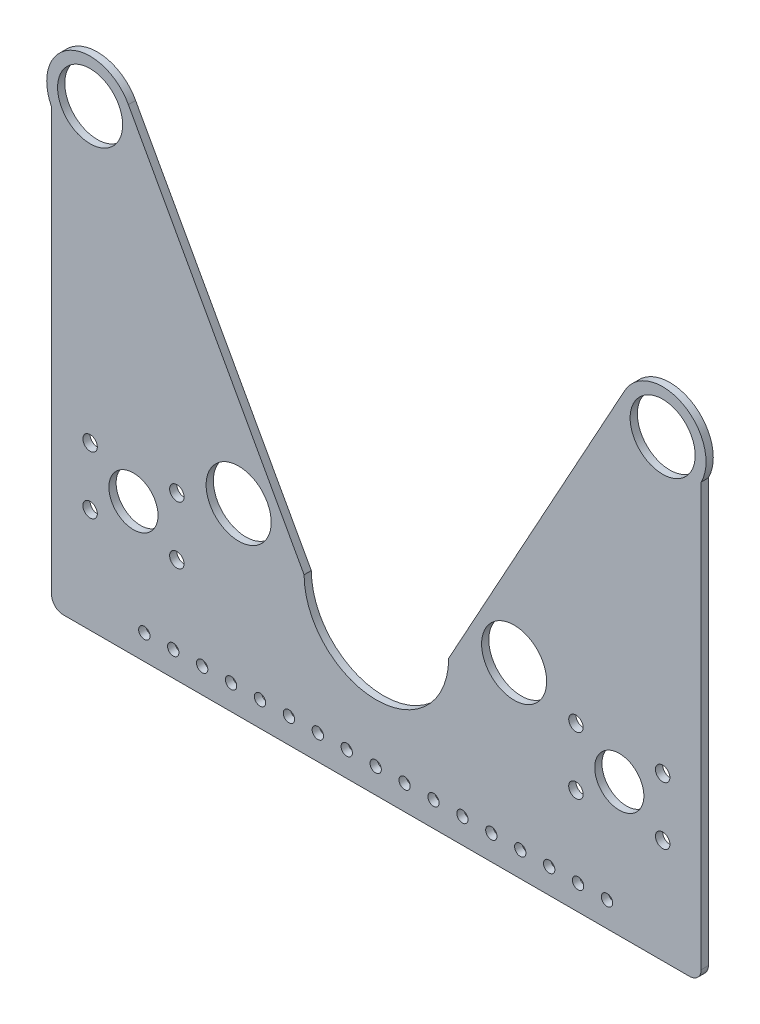
SolidWorks part; units mm, degrees
ref_plane "Front Plane" through (0, 0, 0) normal (0, 0, 1) x (1, 0, 0)
ref_plane "Top Plane" through (0, 0, 0) normal (0, 1, 0) x (1, 0, 0)
ref_plane "Right Plane" through (0, 0, 0) normal (1, 0, 0) x (0, 0, -1)
sketch "Sketch2" plane through (0, 0, 0) normal (0, 0, 1) x (1, 0, 0)
  line L0 (-106.68, -1085.9159) -> (-106.68, 48914.0841) construction
  line L1 (142.6324, 122.4629) -> (142.6324, -29.9371)
  line L2 (106.68, -1098.4025) -> (106.68, 48901.5975) construction
  line L3 (31.75, 0) -> (108.9183, 140.209)
  line L4 (0, -1082.0685) -> (0, 48917.9315) construction
  line L5 (-106.68, -44.45) -> (106.68, -44.45) construction
  line L6 (-106.68, -59.1767) -> (-106.68, -31.75)
  line L7 (0, -31.75) -> (106.68, -31.75) construction
  line L8 (106.68, -55.9582) -> (106.68, -31.75)
  line L9 (-31.75, 0) -> (-108.9183, 140.209)
  line L10 (31.75, 0) -> (108.9183, 140.209)
  line L22 (-142.6324, -57.15) -> (-142.6324, -63.0286)
  line L33 (-106.68, -31.75) -> (0, -31.75) construction
  line L34 (-142.6324, 122.4629) -> (-142.6324, -29.9371)
  line L36 (-261.1394, 46.2048) -> (-243.4617, 46.2048) construction
  line L37 (-243.4617, 46.2048) -> (-243.4617, 28.5272) construction
  line L41 (-238.3305, 62.766) -> (-266.2705, 62.766) construction
  line L42 (-233.2505, 57.686) -> (-233.2505, 17.046) construction
  line L43 (-261.1394, 46.2048) -> (-261.1394, 28.5272) construction
  line L44 (-261.1394, 28.5272) -> (-243.4617, 28.5272) construction
  line L45 (-238.3305, 11.966) -> (-266.2705, 11.966) construction
  line L46 (-271.3505, 57.686) -> (-271.3505, 17.046) construction
  line L47 (-233.2505, 62.766) -> (-271.3505, 11.966) construction
  line L48 (-125.73, 3.175) -> (-125.73, -22.225) construction
  line L49 (-1101.9372, -9.525) -> (48898.0628, -9.525) construction
  line L50 (-233.2505, 11.966) -> (-271.3505, 62.766) construction
  line L51 (-239.6005, 56.416) -> (-239.6005, 18.316) construction
  line L52 (-265.0005, 56.416) -> (-239.6005, 56.416) construction
  line L53 (-125.73, 3.175) -> (-106.68, 3.175) construction
  line L54 (-142.6324, -57.15) -> (142.6324, -57.15) construction
  line L55 (-142.6324, -29.9371) -> (-142.6324, -57.15)
  line L56 (142.6324, -29.9371) -> (142.6324, -57.15)
  line L57 (-137.5524, -68.1086) -> (137.5524, -68.1086)
  line L58 (142.6324, -63.0286) -> (142.6324, -57.15)
  arc A0 (-31.75, 0) -> (31.75, 0) centre (0, 0) ccw
  arc A1 (-108.9183, 140.209) -> (-142.6324, 122.4629) centre (-125.7268, 131.2438) ccw
  circle A2 centre (-60.4845, 12.7) radius 14.2875
  arc A3 (31.75, 0) -> (0, 31.75) centre (0, 0) ccw construction
  arc A4 (0, 31.75) -> (-31.75, 0) centre (0, 0) ccw construction
  arc A5 (137.5524, -68.1086) -> (142.6324, -63.0286) centre (137.5524, -63.0286) ccw
  arc A6 (-142.6324, -63.0286) -> (-137.5524, -68.1086) centre (-137.5524, -63.0286) ccw
  circle A7 centre (-125.7268, 131.2438) radius 14.2875
  circle A9 centre (-60.4845, 12.7) radius 19.05 construction
  circle A10 centre (60.4845, 12.7) radius 19.05 construction
  arc A11 (108.9183, 140.209) -> (142.6324, 122.4629) centre (125.7268, 131.2438) cw
  circle A12 centre (125.7268, 131.2438) radius 14.2875
  circle A34 centre (-101.9175, -57.15) radius 2.4892
  arc A40 (-142.6324, 122.4629) -> (-108.9183, 140.209) centre (-125.7268, 131.2438) ccw construction
  arc A41 (142.6324, 122.4629) -> (108.9183, 140.209) centre (125.7268, 131.2438) cw construction
  circle A42 centre (60.4845, 12.7) radius 14.2875
  circle A43 centre (-89.2175, -57.15) radius 2.4892
  circle A44 centre (-76.5175, -57.15) radius 2.4892
  circle A45 centre (-63.8175, -57.15) radius 2.4892
  circle A46 centre (-51.1175, -57.15) radius 2.4892
  circle A47 centre (-38.4175, -57.15) radius 2.4892
  circle A48 centre (-25.7175, -57.15) radius 2.4892
  circle A49 centre (-13.0175, -57.15) radius 2.4892
  circle A50 centre (-0.3175, -57.15) radius 2.4892
  circle A51 centre (12.3825, -57.15) radius 2.4892
  circle A52 centre (25.0825, -57.15) radius 2.4892
  circle A53 centre (37.7825, -57.15) radius 2.4892
  circle A54 centre (50.4825, -57.15) radius 2.4892
  circle A55 centre (63.1825, -57.15) radius 2.4892
  circle A56 centre (75.8825, -57.15) radius 2.4892
  circle A57 centre (88.5825, -57.15) radius 2.4892
  circle A58 centre (101.2825, -57.15) radius 2.4892
  circle A73 centre (-106.68, -9.525) radius 10.795
  circle A91 centre (-125.73, 3.175) radius 3.175
  circle A92 centre (-125.73, -22.225) radius 3.175
  circle A93 centre (-87.63, -22.225) radius 3.175
  circle A94 centre (-87.63, 3.175) radius 3.175
  circle A95 centre (87.63, -22.225) radius 3.175
  circle A96 centre (87.63, 3.175) radius 3.175
  circle A97 centre (106.68, -9.525) radius 10.795
  circle A98 centre (125.73, -22.225) radius 3.175
  circle A99 centre (125.73, 3.175) radius 3.175
  arc A100 (-260.1552, 27.7564) -> (-262.1235, 29.2979) centre (-261.1394, 28.5272) ccw construction
  arc A101 (-262.1235, 29.2979) -> (-260.1552, 27.7564) centre (-261.1394, 28.5272) ccw construction
  arc A102 (-244.4458, 29.2979) -> (-242.4776, 27.7564) centre (-243.4617, 28.5272) ccw construction
  arc A103 (-242.4776, 27.7564) -> (-244.4458, 29.2979) centre (-243.4617, 28.5272) ccw construction
  arc A104 (-242.4776, 45.4341) -> (-244.4458, 46.9756) centre (-243.4617, 46.2048) ccw construction
  arc A105 (-244.4458, 46.9756) -> (-242.4776, 45.4341) centre (-243.4617, 46.2048) ccw construction
  arc A106 (-262.1235, 46.9756) -> (-260.1552, 45.4341) centre (-261.1394, 46.2048) ccw construction
  arc A107 (-260.1552, 45.4341) -> (-262.1235, 46.9756) centre (-261.1394, 46.2048) ccw construction
  circle A108 centre (-252.3005, 37.366) radius 7.3172 construction
  circle A109 centre (-265.0005, 56.416) radius 3.175 construction
  circle A110 centre (-239.6005, 56.416) radius 3.175 construction
  circle A111 centre (-239.6005, 18.316) radius 3.175 construction
  circle A112 centre (-265.0005, 18.316) radius 3.175 construction
  arc A113 (-266.2705, 11.966) -> (-271.3505, 17.046) centre (-266.2705, 17.046) cw construction
  arc A114 (-233.2505, 17.046) -> (-238.3305, 11.966) centre (-238.3305, 17.046) cw construction
  arc A115 (-238.3305, 62.766) -> (-233.2505, 57.686) centre (-238.3305, 57.686) cw construction
  arc A116 (-266.2705, 62.766) -> (-271.3505, 57.686) centre (-266.2705, 57.686) ccw construction
  point P26 (0, 0)
  point P27 (0, 0)
  point P91 (0, 0)
  point P92 (142.6324, -57.8385)
  point P154 (-125.73, -9.525)
  dimension "D7" = 131.2438
  dimension "D8" = 101.9175
  dimension "D9" = 25.4
  dimension "D3" = 44.45
  dimension "D14" = 106.68
  dimension "D17" = 38.1
  dimension "D5" = 5.08
  dimension "D15" = 31.75
  dimension "D16" = 28.575
  dimension "D18" = 28.575
  dimension "D19" = 19.05
  dimension "D21" = 125.7268
  dimension "D27" = 22.225
  dimension "D28" = 21.59
  dimension "D33" = 6.35
  dimension "D35" = 8.8388
  dimension "D37" = 8.8388
  dimension "D46" = 6.35
  dimension "D34" = 6.35
  dimension "D36" = 1.25
  dimension "D38" = 5.08
  dimension "D1" = 28.828
  dimension "D6" = 10.9586
  dimension "D10" = 17
  dimension "D20" = 142.6324
  dimension "D25" = 152.4
  dimension "D26" = 12.7
  dimension "D32" = 6.35
  dimension "D29" = 17.6777
  dimension "D30" = 50.8
  dimension "D31" = 38.1
  dimension "D39" = 25.4
  dimension "D40" = 38.1
  dimension "D41" = 16.9024
extrude "Boss-Extrude1" add sketch "Sketch2" along normal blind 3.175 contours A11 L3 A0 L9 A1 L6 L8 A58 A57 A56 A55 region at (139.0055, 46.2629, 0)
